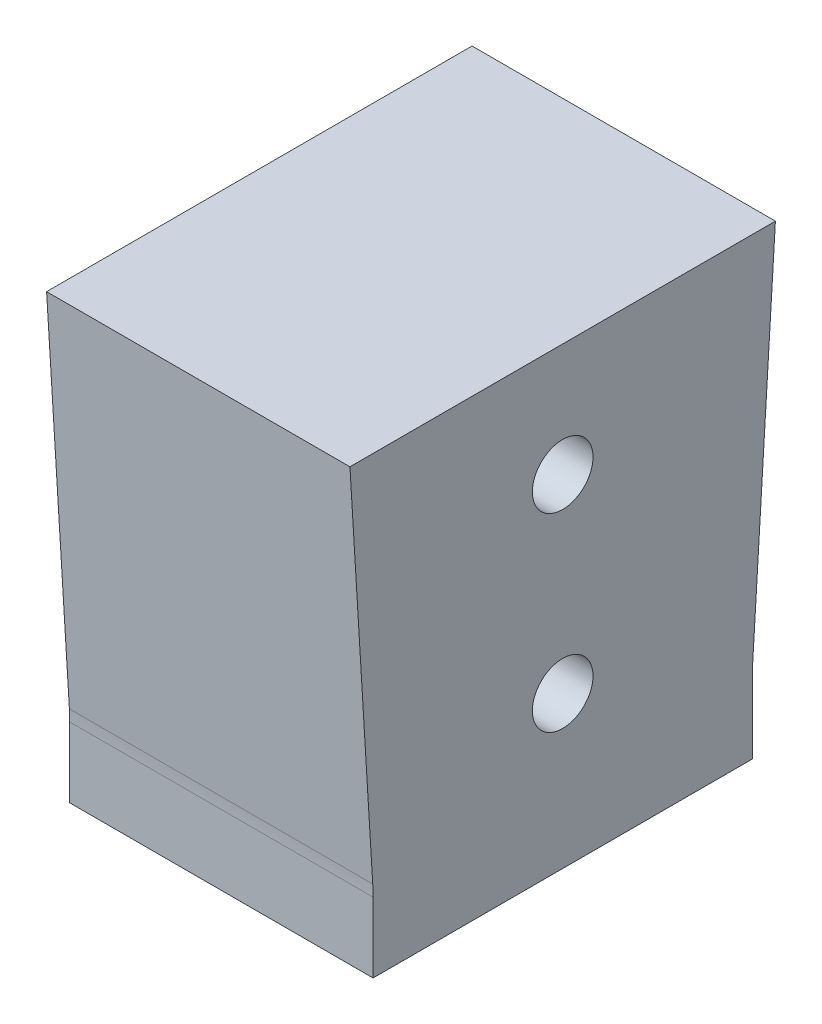
SolidWorks part; units mm, degrees
ref_plane "前视基准面" through (0, 0, 0) normal (0, 0, 1) x (1, 0, 0)
ref_plane "上视基准面" through (0, 0, 0) normal (0, 1, 0) x (1, 0, 0)
ref_plane "右视基准面" through (0, 0, 0) normal (1, 0, 0) x (0, 0, -1)
other "Configuration Table"
sketch "草图1" plane through (0, 0, 0) normal (0, 0, 1) x (1, 0, 0)
  line L0 (0, 30.9904) -> (0, -26.9724)
  line L2 (0, -5.8517) -> (-3, -5.8517)
  line L3 (0, -5.8517) -> (0, 8.1483)
  line L4 (-3, 8.1243) -> (-3, -5.8517)
  arc A1 (0, 15.1483) -> (-15.8883, 4.195) centre (0, -1.8517) ccw
  arc A2 (-15.8883, 4.195) -> (-13.8622, 2.8411) centre (-14.7201, 3.7503) ccw
  arc A4 (-3, 8.1243) -> (-13.8622, 2.8411) centre (0, -11.8517) ccw construction
  arc A5 (-3, 8.1243) -> (-13.8622, 2.8411) centre (0, -11.8517) ccw
  dimension "D3" = 34
  dimension "D4" = 2.5
  dimension "D2" = 10
  dimension "D6" = 6
revolve "旋转1" add sketch "草图1" angle 360 about L0 region at (-0.2638, 11.6483, 0)
sketch "草图3" plane through (0, 0, 0) normal (0, 0, 1) x (1, 0, 0)
  line L0 (0, 16.9635) -> (0, -17.5808) construction
ref_plane "基准面1" through (0, 15.1483, 0) normal (0, -1, 0) x (-1, 0, 0)
sketch "草图4" plane through (0, 15.1483, 0) normal (0, -1, 0) x (-1, 0, 0)
  line L0 (12.5453, 0) -> (-13.8264, 0) construction
  line L2 (8, 10) -> (-8, 10)
  line L3 (8, 10) -> (8, -10)
  line L4 (8, -10) -> (-8, -10)
  line L5 (-8, 10) -> (-8, -10)
  line L6 (8, 10) -> (-8, -10) construction
  line L7 (8, -10) -> (-8, 10) construction
  point P3 (0, 0)
  dimension "D1" = 16
  dimension "D2" = 20
extrude "凸台-拉伸1" add sketch "草图4" along normal up to next
sketch "草图7" plane through (0, 0, 0) normal (1, 0, 0) x (0, 0, -1)
  line L0 (-10, 15.1483) -> (-11.221, 35.111)
  line L1 (0, 16.9635) -> (0, -17.5808) construction
  line L2 (0, 33.3667) -> (0, -6.8807) construction
  line L3 (-11.221, 35.111) -> (11.221, 35.111)
  line L4 (10, 15.1483) -> (11.221, 35.111)
  line L5 (-10, 15.1483) -> (10, 15.1483)
  circle A0 centre (0, 29.1483) radius 1.6
  circle A1 centre (0, 19.1483) radius 1.6
  point P10 (0, 35.111)
  dimension "D3" = 3.2
  dimension "D4" = 4
  dimension "D5" = 3.2
  dimension "D6" = 10
  dimension "D1" = 3.5
  dimension "D2" = 20
extrude "凸台-拉伸2" add sketch "草图7" along normal mid plane 16
fillet "圆角1" radius 2 1 edges at (0, 8.1243, 3)
sketch "草图8" plane through (8, 0, 0) normal (1, 0, 0) x (0, 0, -1)
  line L0 (-10, 15.1483) -> (10, 15.1483)
  line L1 (-10, 15.1483) -> (-23.1228, 15.1483)
  line L2 (-23.1228, 15.1483) -> (-23.1228, -11.3342)
  line L3 (-23.1228, -11.3342) -> (22.0744, -11.3342)
  line L4 (22.0744, -11.3342) -> (22.0744, 15.1483)
  line L5 (22.0744, 15.1483) -> (10, 15.1483)
extrude "切除-拉伸1" cut sketch "草图8" against normal blind 28 and the other way blind 10 contours L5 L0 L1 L2 L3 L4
sketch "草图9" plane through (0, 15.1483, 0) normal (0, -1, 0) x (1, 0, 0)
  line L4 (-8, -10) -> (8, -10)
  line L5 (8, -10) -> (8, 10)
  line L6 (8, 10) -> (-8, 10)
  line L7 (-8, 10) -> (-8, -10)
  line L8 (-8, -10) -> (8, -10)
  line L9 (8, -10) -> (8, 10)
  line L10 (8, 10) -> (-8, 10)
  line L11 (-8, 10) -> (-8, -10)
  dimension "D1" = 0
extrude "凸台-拉伸3" add sketch "草图9" along normal blind 4
fillet "圆角2" radius 10 2 edges at (0, 15.1483, 10) (0, 15.1483, -10)
